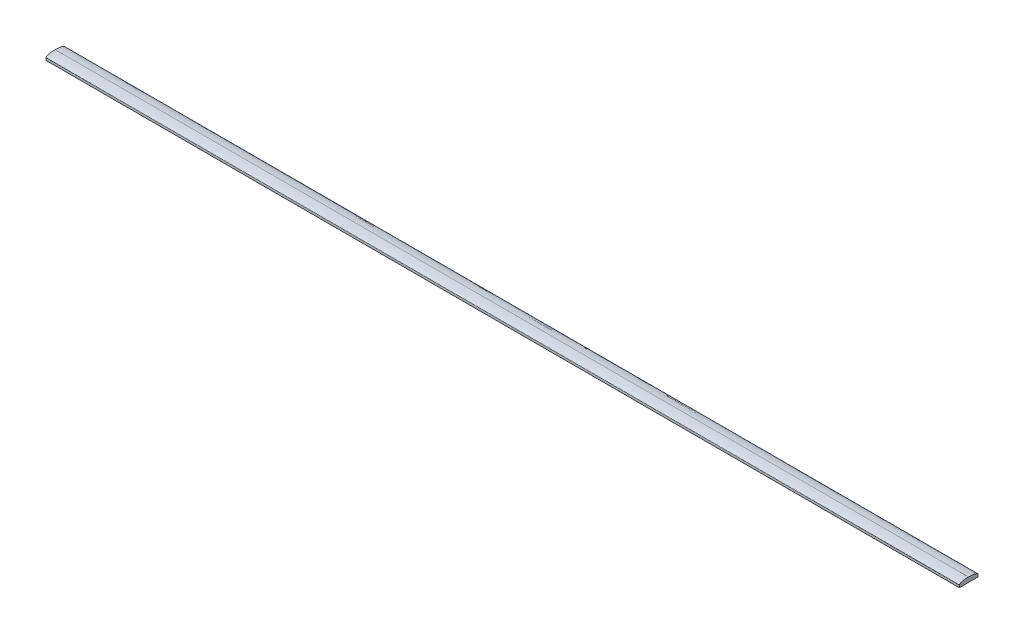
SolidWorks part; units mm, degrees
ref_plane "Front Plane" through (0, 0, 0) normal (0, 0, 1) x (1, 0, 0)
ref_plane "Top Plane" through (0, 0, 0) normal (0, 1, 0) x (1, 0, 0)
ref_plane "Right Plane" through (0, 0, 0) normal (1, 0, 0) x (0, 0, -1)
sketch "Sketch1" plane through (0, 0, 0) normal (0, 1, 0) x (1, 0, 0)
  line L1 (0, 0) -> (488.95, 0)
  line L2 (0, 0) -> (0, 10)
  line L3 (0, 10) -> (488.95, 10)
  line L4 (488.95, 0) -> (488.95, 10)
  dimension "D1" = 10
  dimension "Strip Length" = 488.95
extrude "Boss-Extrude1" add sketch "Sketch1" along normal blind 2.54
fillet "Fillet5" radius 1.27 2 edges at (244.475, 2.54, -10) (244.475, 2.54, 0) second distance 5.08 first distance on face at (244.475, 1.27, -10) first distance on face at (244.475, 1.27, 0)
